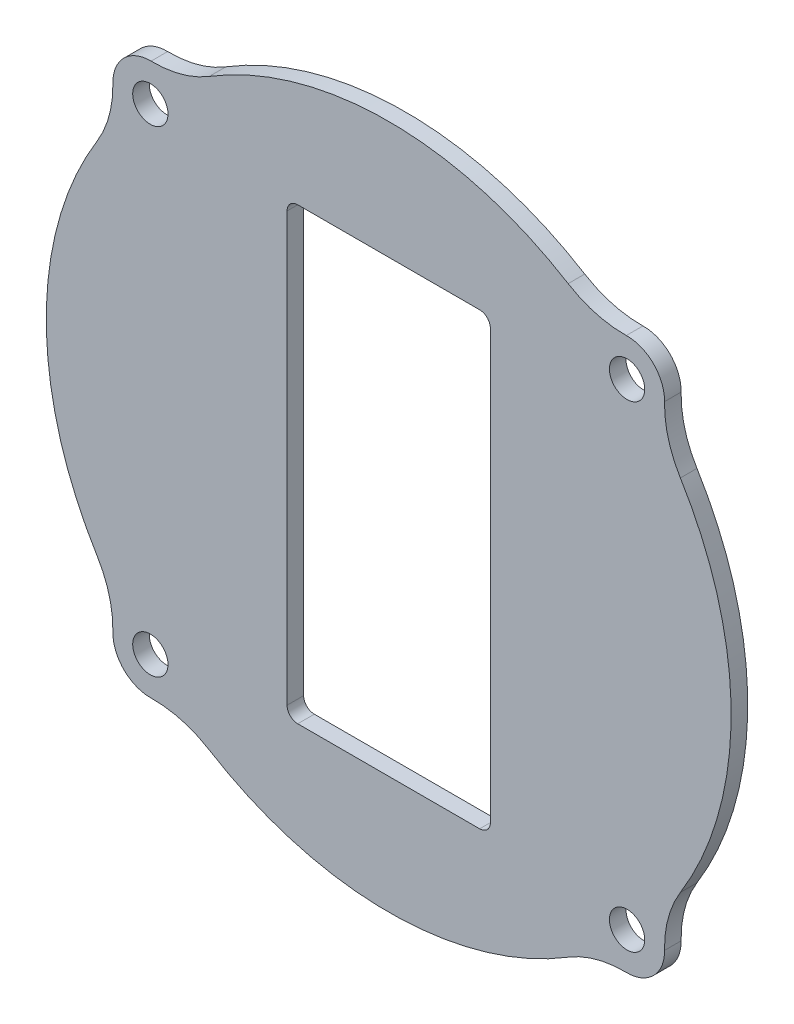
SolidWorks part; units mm, degrees
material "Epoxy, renforcé"
ref_plane "Plan de face" through (0, 0, 0) normal (0, 0, 1) x (1, 0, 0)
ref_plane "Plan de dessus" through (0, 0, 0) normal (0, 1, 0) x (1, 0, 0)
ref_plane "Plan de droite" through (0, 0, 0) normal (1, 0, 0) x (0, 0, -1)
sketch "Esquisse1" plane through (0, 0, 0) normal (0, 0, 1) x (1, 0, 0)
  line L0 (0, 31.5) -> (0, 0) construction
  line L1 (15.5, 21) -> (-15.5, 21) construction
  line L2 (15.5, 21) -> (15.5, -21) construction
  line L3 (15.5, -21) -> (-15.5, -21) construction
  line L4 (-15.5, 21) -> (-15.5, -21) construction
  line L5 (15.5, 21) -> (-15.5, -21) construction
  line L6 (15.5, -21) -> (-15.5, 21) construction
  line L7 (0, 0) -> (-22.2739, 22.2739) construction
  arc A0 (-24.9579, 20.0276) -> (-24.9579, -20.0276) centre (0, 0) ccw
  circle A1 centre (0, 0) radius 31.5 construction
  circle A2 centre (-22.2739, 22.2739) radius 1.65
  circle A3 centre (22.2739, 22.2739) radius 1.65
  circle A4 centre (22.2739, -22.2739) radius 1.65
  circle A5 centre (-22.2739, -22.2739) radius 1.65
  arc A6 (-20.0276, 24.9579) -> (-24.9579, 20.0276) centre (-22.2739, 22.2739) ccw
  arc A7 (24.9579, 20.0276) -> (20.0276, 24.9579) centre (22.2739, 22.2739) ccw
  arc A8 (20.0276, -24.9579) -> (24.9579, -20.0276) centre (22.2739, -22.2739) ccw
  arc A9 (-24.9579, -20.0276) -> (-20.0276, -24.9579) centre (-22.2739, -22.2739) ccw
  arc A10 (20.0276, 24.9579) -> (-20.0276, 24.9579) centre (0, 0) ccw
  arc A11 (24.9579, -20.0276) -> (24.9579, 20.0276) centre (0, 0) ccw
  arc A13 (-20.0276, -24.9579) -> (20.0276, -24.9579) centre (0, 0) ccw
  point P0 (0, 0)
  point P21 (0, 0)
  point P29 (0, 0)
  dimension "D3" = 63
  dimension "D5" = 3.3
  dimension "D7" = 64
  dimension "D9" = 7
  dimension "D1" = 31
  dimension "D2" = 42
  dimension "D4" = 45
  dimension "D6" = 4
  dimension "D8" = 4
extrude "Boss.-Extru.1" add sketch "Esquisse1" along normal blind 1.55
sketch "Esquisse2" plane through (0, 0, 1.55) normal (0, 0, 1) x (1, 0, 0)
  line L1 (9.5, 21) -> (-9.5, 21)
  line L2 (9.5, 21) -> (9.5, -21)
  line L3 (9.5, -21) -> (-9.5, -21)
  line L4 (-9.5, 21) -> (-9.5, -21)
  line L5 (9.5, 21) -> (-9.5, -21) construction
  line L6 (9.5, -21) -> (-9.5, 21) construction
  point P0 (0, 0)
  dimension "D1" = 19
  dimension "D2" = 42
extrude "Enlèv. mat.-Extru.1" cut sketch "Esquisse2" against normal through all
fillet "Congé1" radius 10 8 edges at (24.9579, -20.0276, 0.775) (20.0276, -24.9579, 0.775) (-20.0276, -24.9579, 0.775) (-24.9579, -20.0276, 0.775) (-24.9579, 20.0276, 0.775) (-20.0276, 24.9579, 0.775) (20.0276, 24.9579, 0.775) (24.9579, 20.0276, 0.775)
fillet "Congé2" radius 1 4 edges at (9.5, 21, 0.775) (9.5, -21, 0.775) (-9.5, -21, 0.775) (-9.5, 21, 0.775)
